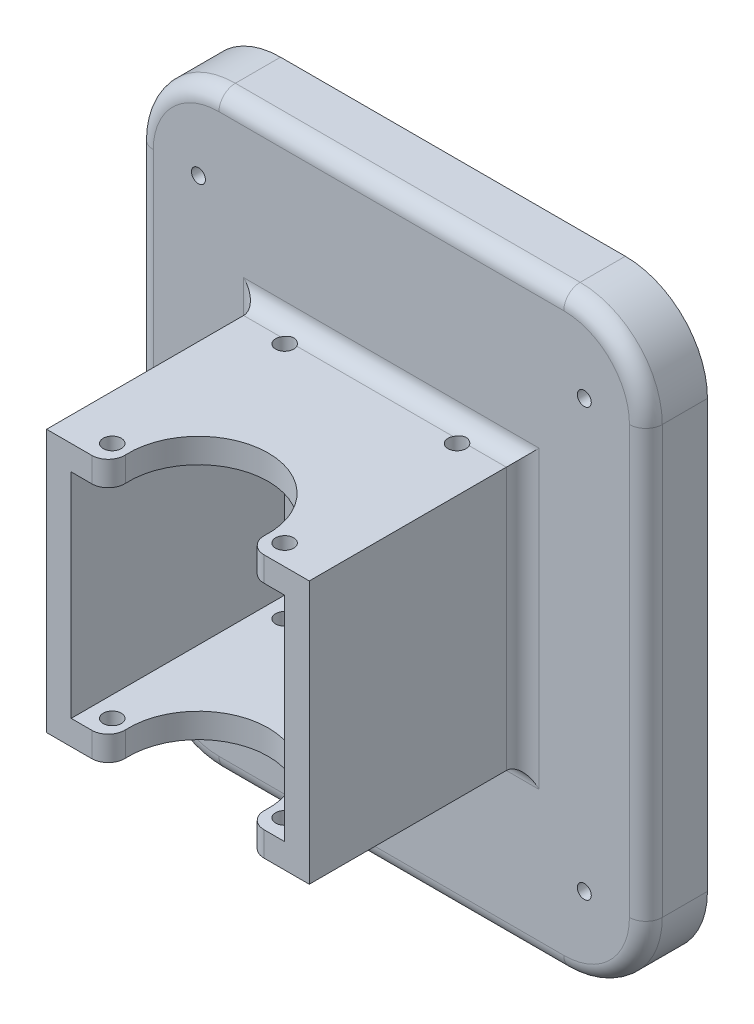
SolidWorks part; units mm, degrees
material "ABS"
ref_plane "正面" through (0, 0, 0) normal (0, 0, 1) x (1, 0, 0)
ref_plane "平面" through (0, 0, 0) normal (0, 1, 0) x (1, 0, 0)
ref_plane "右側面" through (0, 0, 0) normal (1, 0, 0) x (0, 0, -1)
sketch "ｽｹｯﾁ2" plane through (0, 0, 0) normal (0, 0, 1) x (1, 0, 0)
  line L0 (19.8, 0) -> (-19.8, 0) construction
  line L1 (-16, 0) -> (16, 0)
  line L2 (-16, 0) -> (-16, 32)
  line L3 (-16, 32) -> (16, 32)
  line L4 (16, 0) -> (16, 32)
  line L5 (-13, 3) -> (13, 3)
  line L6 (13, 3) -> (13, 29)
  line L7 (-13, 29) -> (13, 29)
  line L8 (-13, 3) -> (-13, 29)
  dimension "D1" = 32
  dimension "D2" = 32
  dimension "D3" = 3
extrude "ﾎﾞｽ - 押し出し1" add sketch "ｽｹｯﾁ2" along normal blind 26
sketch "ｽｹｯﾁ3" plane through (0, 0, 0) normal (0, 0, -1) x (-1, 0, 0)
  line L5 (-16, 0) -> (-16, 32) construction
  line L6 (-31, 52) -> (31, 52)
  line L7 (-31, 52) -> (-31, -20)
  line L8 (-31, -20) -> (31, -20)
  line L9 (31, 52) -> (31, -20)
  line L10 (16, 32) -> (16, 0) construction
  line L11 (-16, 32) -> (16, 32) construction
  line L12 (15.675, 0) -> (-15.675, 0) construction
  dimension "D1" = 15
  dimension "D2" = 15
  dimension "D3" = 20
  dimension "D4" = 20
extrude "ﾎﾞｽ - 押し出し2" add sketch "ｽｹｯﾁ3" along normal blind 7.5
fillet "ﾌｨﾚｯﾄ1" radius 2 4 edges at (0, 0, 0) (16, 16, 0) (-16, 16, 0) (0, 32, 0)
fillet "ﾌｨﾚｯﾄ2" radius 2 4 edges at (-31, 16, 0) (0, 52, 0) (31, 16, 0) (0, -20, 0)
sketch "ｽｹｯﾁ5" plane through (0, 0, 0) normal (0, -1, 0) x (1, 0, 0)
  line L0 (0, 26) -> (0, 0) construction
  line L1 (-16, 26) -> (16, 26) construction
  line L3 (-10.5, 23.5) -> (10.5, 23.5) construction
  line L4 (-10.5, 23.5) -> (-10.5, 2.5) construction
  line L5 (-10.5, 2.5) -> (10.5, 2.5) construction
  line L6 (10.5, 23.5) -> (10.5, 2.5) construction
  line L7 (-10.5, 23.5) -> (10.5, 2.5) construction
  line L8 (-10.5, 2.5) -> (10.5, 23.5) construction
  circle A0 centre (10.5, 23.5) radius 1.1
  circle A1 centre (-10.5, 23.5) radius 1.1
  circle A2 centre (-10.5, 2.5) radius 1.1
  circle A3 centre (10.5, 2.5) radius 1.1
  circle A4 centre (0, 23.5) radius 8.5
  point P5 (0, 13)
  dimension "D4" = 2.2
  dimension "D5" = 17
  dimension "D1" = 21
  dimension "D2" = 21
  dimension "D3" = 13
extrude "ｶｯﾄ - 押し出し1" cut sketch "ｽｹｯﾁ5" against normal through all both and the other way through all
fillet "ﾌｨﾚｯﾄ3" radius 2 4 edges at (-8.124, 30.5, 26) (8.124, 30.5, 26) (-8.124, 1.5, 26) (8.124, 1.5, 26)
sketch "ｽｹｯﾁ7" plane through (0, 0, -7.5) normal (0, 0, -1) x (-1, 0, 0)
  line L1 (-23.5, -10) -> (23.5, -10) construction
  line L2 (-23.5, -10) -> (-23.5, 42) construction
  line L3 (-23.5, 42) -> (23.5, 42) construction
  line L4 (-31, 52) -> (-31, -20)
  line L5 (-31, -20) -> (31, -20)
  line L6 (31, -20) -> (31, 52)
  line L7 (31, 52) -> (-31, 52)
  line L8 (-31, 52) -> (-31, -20) construction
  line L9 (-31, -20) -> (31, -20) construction
  line L10 (31, -20) -> (31, 52) construction
  line L11 (31, 52) -> (-31, 52) construction
  line L12 (23.5, -10) -> (23.5, 42) construction
  circle A0 centre (-23.5, -10) radius 0.85
  circle A1 centre (-23.5, 42) radius 0.85
  circle A2 centre (23.5, 42) radius 0.85
  circle A3 centre (23.5, -10) radius 0.85
  dimension "D6" = 1.7
  dimension "D2" = 10
  dimension "D3" = 10
  dimension "D4" = 7.5
  dimension "D5" = 7.5
  dimension "D1" = 0
extrude "ｶｯﾄ - 押し出し2" cut sketch "ｽｹｯﾁ7" against normal through all
fillet "ﾌｨﾚｯﾄ4" radius 10 8 edges at (-30.4142, 51.4142, -0.5858) (-30.4142, -19.4142, -0.5858) (30.4142, -19.4142, -0.5858) (30.4142, 51.4142, -0.5858) (31, 52, -4.75) (31, -20, -4.75) (-31, -20, -4.75) (-31, 52, -4.75)
